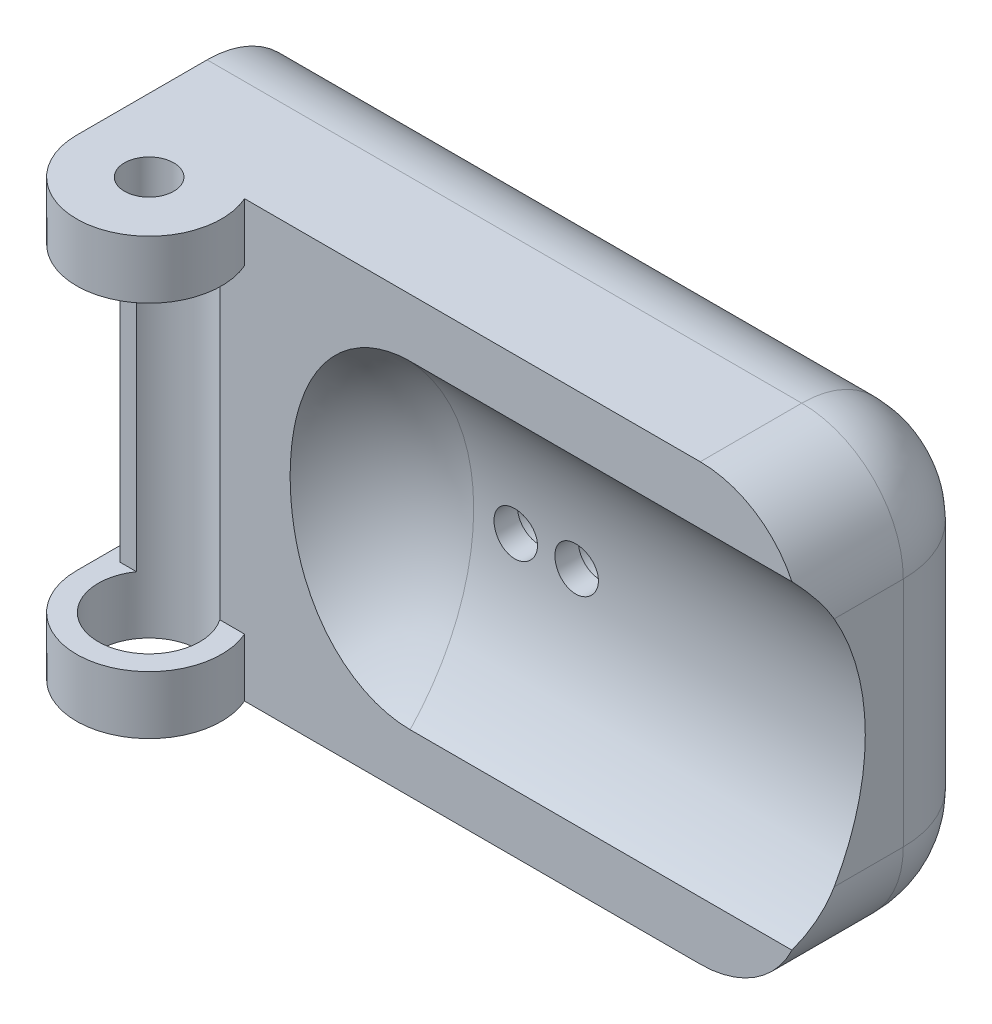
SolidWorks part; units mm, degrees
ref_plane "Alzado" through (0, 0, 0) normal (0, 0, 1) x (1, 0, 0)
ref_plane "Planta" through (0, 0, 0) normal (0, 1, 0) x (1, 0, 0)
ref_plane "Vista lateral" through (0, 0, 0) normal (1, 0, 0) x (0, 0, -1)
sketch "Croquis1" plane through (0, 0, 0) normal (0, 0, 1) x (1, 0, 0)
  line L1 (-43.9768, 15.9874) -> (4.0232, 15.9874)
  line L2 (-43.9768, 15.9874) -> (-43.9768, -14.0126)
  line L3 (-43.9768, -14.0126) -> (4.0232, -14.0126)
  line L4 (4.0232, 15.9874) -> (4.0232, -14.0126)
  dimension "D1" = 48
  dimension "D2" = 30
extrude "Saliente-Extruir1" add sketch "Croquis1" along normal blind 14
sketch "Croquis2" plane through (4.0232, 0, 0) normal (1, 0, 0) x (0, 0, -1)
  line L0 (-14, 15.9874) -> (-14, 11.9874) construction
  line L1 (-14, -14.0126) -> (-14, 15.9874) construction
  line L2 (-14, -14.0126) -> (-14, -10.0126) construction
  line L3 (-14, -14.0126) -> (0, -14.0126) construction
  line L4 (-14, 15.9874) -> (0, 15.9874) construction
  line L5 (-14, 0.9874) -> (-37.2379, 0.9874) construction
  line L6 (-14, 11.9874) -> (-14, -10.0126)
  arc A0 (-14, 11.9874) -> (-14, -10.0126) centre (-25.619, 0.9874) cw
  line M3 (-14, 15.9874) -> (-14, -14.0126)
  dimension "D1" = 4
  dimension "D2" = 4
extrude "Cortar-Extruir1" cut sketch "Croquis2" against normal blind 37 contours A0 M3 region at (4.0232, 0.9874, 12.2252)
fillet "Redondeo1" [suppressed] radius 2
fillet "Redondeo2" radius 7 5 edges at (-19.9768, -14.0126, 0) (4.0232, 0.9874, 0) (-19.9768, 15.9874, 0) (4.0232, 15.9874, 7) (4.0232, -14.0126, 7)
sketch "Croquis3" plane through (0, 0, 0) normal (0, 0, -1) x (-1, 0, 0)
  line L1 (2.9768, -7.0126) -> (43.9768, -7.0126) construction
  line L2 (28.9768, -7.0126) -> (8.9768, -7.0126)
  line L3 (28.9768, -7.0126) -> (28.9768, 8.9874)
  line L4 (28.9768, 8.9874) -> (8.9768, 8.9874)
  line L5 (8.9768, -7.0126) -> (8.9768, 8.9874)
  line L6 (43.9768, 8.9874) -> (2.9768, 8.9874) construction
  line L7 (43.9768, 8.9874) -> (43.9768, -7.0126) construction
  dimension "D1" = 15
  dimension "D2" = 20
extrude "Cortar-Extruir2" cut sketch "Croquis3" against normal blind 3
sketch "Croquis5" plane through (0, 0, 0) normal (0, 0, -1) x (-1, 0, 0)
  line L0 (43.9768, 0.9874) -> (24.1183, 0.9874) construction
  line L1 (43.9768, 8.9874) -> (43.9768, -7.0126) construction
  line L2 (17.9768, -2.7686) -> (17.9768, -8.4151) construction
  circle A0 centre (20.0768, 0.9874) radius 1.5
  circle A1 centre (15.8768, 0.9874) radius 1.5
  dimension "D2" = 3
  dimension "D1" = 3
  dimension "D3" = 2.1
  dimension "D4" = 2.1
extrude "Cortar-Extruir3" cut sketch "Croquis5" against normal blind 12
sketch "Croquis6" plane through (0, 0, 3) normal (0, 0, -1) x (-1, 0, 0)
  line L0 (17.9768, 0.9874) -> (12.7401, 0.9874) construction
  line L1 (17.9768, 0.9874) -> (17.9768, 7.5082) construction
  line L3 (22.9768, -2.5126) -> (12.9768, -2.5126)
  line L4 (22.9768, -2.5126) -> (22.9768, 4.4874)
  line L5 (22.9768, 4.4874) -> (12.9768, 4.4874)
  line L6 (12.9768, -2.5126) -> (12.9768, 4.4874)
  point P8 (0, 0)
  dimension "D1" = 3.5
  dimension "D2" = 3.5
  dimension "D3" = 5
  dimension "D4" = 5
extrude "Cortar-Extruir4" [suppressed] cut sketch "Croquis6" against normal blind 8
sketch "Croquis7" [suppressed] plane through (0, 0, 3) normal (0, 0, -1) x (-1, 0, 0)
  line L0 (22.9768, 4.4874) -> (12.9768, 4.4874) construction
  line L1 (24.9768, -5.5126) -> (10.9768, -5.5126)
  line L2 (24.9768, -5.5126) -> (24.9768, 7.4874)
  line L3 (24.9768, 7.4874) -> (10.9768, 7.4874)
  line L4 (10.9768, -5.5126) -> (10.9768, 7.4874)
  line L5 (12.9768, -2.5126) -> (22.9768, -2.5126) construction
  line L6 (12.9768, 4.4874) -> (12.9768, -2.5126) construction
  line L7 (22.9768, -2.5126) -> (22.9768, 4.4874) construction
  dimension "D1" = 3
  dimension "D2" = 3
  dimension "D3" = 2
  dimension "D4" = 2
extrude "Cortar-Extruir5" [suppressed] cut sketch "Croquis7" against normal blind 5
sketch "Croquis8" [suppressed] plane through (-24.9768, 0, 0) normal (1, 0, 0) x (0, 0, -1)
  circle A0 centre (-5.9042, 0) radius 1.5
  dimension "D1" = 3
extrude "Cortar-Extruir6" [suppressed] cut sketch "Croquis8" against normal up to surface (19 mm away)
sketch "Croquis9" plane through (0, 0, 3) normal (0, 0, -1) x (-1, 0, 0)
  circle A0 centre (20.0768, 0.9874) radius 2
  circle A1 centre (15.8768, 0.9874) radius 2
  dimension "D1" = 4
  dimension "D2" = 4
extrude "Cortar-Extruir8" [suppressed] cut sketch "Croquis9" against normal blind 5 contours A0
sketch "Croquis10" plane through (0, 0, 3) normal (0, 0, -1) x (-1, 0, 0)
  circle A0 centre (17.9839, 0.9874) radius 6.9277
extrude "Cortar-Extruir9" cut sketch "Croquis10" against normal blind 3
sketch "Croquis11" plane through (-43.9768, 0, 0) normal (-1, 0, 0) x (0, 0, 1)
  line L0 (0, 0.9874) -> (16.3469, 0.9874) construction
  line L1 (0, 8.9874) -> (0, -7.0126) construction
  circle A0 centre (4.2365, 0.9874) radius 3
  dimension "D1" = 6
extrude "Cortar-Extruir10" cut sketch "Croquis11" against normal up to surface (19.7484 mm away) up to face at (-24.9116, 0.9874, 6)
sketch "Croquis12" plane through (0, -14.0126, 0) normal (0, -1, 0) x (1, 0, 0)
  line L1 (-43.9768, 14) -> (-2.9768, 14) construction
  line L4 (-43.9768, 14) -> (-43.9768, 7) construction
  circle A0 centre (-38.9768, 16) radius 3.5
  point P0 (-38.9768, 14)
  dimension "D3" = 5
  dimension "D1" = 2
  dimension "D2" = 0
sketch "Croquis14" plane through (0, -14.0126, 0) normal (0, -1, 0) x (1, 0, 0)
  line L1 (-43.9768, 14) -> (-2.9768, 14) construction
  line L2 (-43.9768, 14) -> (-43.9768, 7) construction
  line L3 (-43.9768, 16) -> (-43.9768, 14)
  line L4 (-43.9768, 14) -> (-43.5593, 14)
  circle A0 centre (-38.9768, 16) radius 5
  line M3 (-2.9768, 14) -> (-43.9768, 14)
  dimension "D1" = 2
  dimension "D2" = 5
extrude "Saliente-Extruir5" add sketch "Croquis14" against normal blind 4 contours A0 M3 | A0 L3 M3 region at (-43.8525, -14.0126, 14.4957) region at (-38.9768, -14.0126, 17.0925)
ref_plane "Plano2" through (0, 0.9874, 0) normal (0, 1, 0) x (-1, 0, 0)
mirror "Simetría1" about plane through (0, 0.9874, 0) normal (0, 1, 0) of "Saliente-Extruir5"
extrude "Cortar-Extruir14" cut sketch "Croquis12" against normal up to surface (26 mm away) up to face at (-40.3725, 11.9874, 16.6315)
ref_plane "Plano3" through (0, -10.0126, 0) normal (0, -1, 0) x (1, 0, 0)
sketch "Croquis15" plane through (0, -10.0126, 0) normal (0, -1, 0) x (1, 0, 0)
  line L0 (-43.9768, 16) -> (-43.9768, 12)
  line L1 (-43.9768, 16) -> (-43.9768, 7) construction
  line L2 (-43.9768, 12) -> (-41.9768, 16)
  line L3 (-41.9768, 16) -> (-43.9768, 16)
  dimension "D1" = 4
  dimension "D2" = 2
extrude "Cortar-Extruir16" cut sketch "Croquis15" against normal blind 22
sketch "Croquis16" plane through (0, 0, 6) normal (0, 0, -1) x (-1, 0, 0)
  circle A0 centre (15.8768, 0.9874) radius 2
  circle A1 centre (20.0768, 0.9874) radius 2
  dimension "D1" = 4
extrude "Cortar-Extruir17" cut sketch "Croquis16" against normal blind 2
sketch "Croquis17" plane through (0, 0, 0) normal (0, 0, -1) x (-1, 0, 0)
  line L0 (28.9768, -7.0126) -> (28.9768, 8.9874) construction
  line L1 (28.9768, 3.4874) -> (31.9768, 3.4874)
  line L2 (28.9768, 3.4874) -> (28.9768, -1.5126)
  line L3 (28.9768, -1.5126) -> (31.9768, -1.5126)
  line L4 (31.9768, 3.4874) -> (31.9768, -1.5126)
  line L5 (43.9768, 0.9874) -> (38.4335, 0.9874) construction
  line L6 (43.9768, 8.9874) -> (43.9768, -7.0126) construction
  dimension "D1" = 5
  dimension "D2" = 3
  dimension "D3" = 2.5
extrude "Cortar-Extruir18" cut sketch "Croquis17" against normal blind 3
sketch "Croquis18" plane through (0, 15.9874, 0) normal (0, 1, 0) x (1, 0, 0)
  circle A0 centre (-38.9768, -16) radius 1.7
extrude "Cortar-Extruir19" cut sketch "Croquis18" against normal up to surface (4 mm away) up to face at (-40.3413, 11.9874, 14.7324)
fillet "Redondeo3" radius 10 1 edges at (-32.9768, 0.9874, 9.619)
